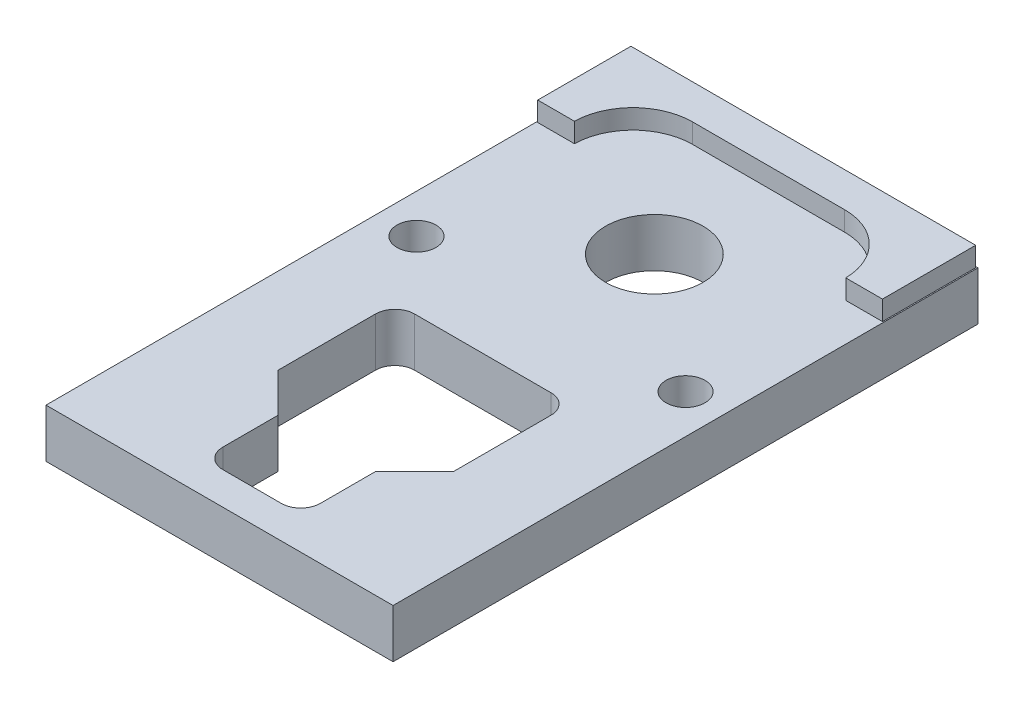
SolidWorks part; units mm, degrees
ref_plane "Płaszczyzna przednia" through (0, 0, 0) normal (0, 0, 1) x (1, 0, 0)
ref_plane "Płaszczyzna górna" through (0, 0, 0) normal (0, 1, 0) x (1, 0, 0)
ref_plane "Płaszczyzna prawa" through (0, 0, 0) normal (1, 0, 0) x (0, 0, -1)
sketch "Sketch1" plane through (0, 0, 0) normal (0, 1, 0) x (1, 0, 0)
  line L0 (-6.9, 0) -> (6.9, 0) construction
  line L2 (-8.9, 13) -> (8.9, 13)
  line L3 (-8.9, 13) -> (-8.9, -17)
  line L4 (-8.9, -17) -> (8.9, -17)
  line L5 (8.9, 13) -> (8.9, -17)
  circle A0 centre (-6.9, 0) radius 1
  circle A1 centre (6.9, 0) radius 1
  circle A2 centre (6.9, 0) radius 2 construction
  circle A3 centre (-6.9, 0) radius 2 construction
  circle A4 centre (0, 5.3) radius 2.5
  point P4 (0, 0)
  dimension "D2" = 2
  dimension "D4" = 5
  dimension "D5" = 5.3
  dimension "D1" = 13.8
  dimension "D6" = 13
  dimension "D7" = 17
  dimension "D3" = 1
extrude "Boss-Extrude1" add sketch "Sketch1" along normal blind 2.5
sketch "Sketch2" plane through (0, 2.5, 0) normal (0, 1, 0) x (1, 0, 0)
  line L0 (0, -3.5) -> (0, 0) construction
  line L1 (-4.5, -3.5) -> (4.5, -3.5)
  line L2 (-4.5, -3.5) -> (-4.5, -9.5)
  line L3 (-4.5, -9.5) -> (4.5, -9.5)
  line L4 (4.5, -3.5) -> (4.5, -9.5)
  line L5 (0, -15.3309) -> (0, 0) construction
  line L6 (-2.5, -9.5) -> (2.5, -9.5)
  line L7 (-2.5, -9.5) -> (-2.5, -15.3309)
  line L8 (-2.5, -15.3309) -> (2.5, -15.3309)
  line L9 (2.5, -9.5) -> (2.5, -15.3309)
  dimension "D1" = 9
  dimension "D2" = 6
  dimension "D3" = 3.5
  dimension "D4" = 5
extrude "Cut-Extrude1" cut sketch "Sketch2" against normal through all contours L4 L1 L2 L3 | L9 L3 L7 L8 region at (0, 2.5, 6.5) region at (0, 2.5, 12.4155)
chamfer "Chamfer1" distance 2 angle 45 2 edges at (2.5, 1.25, 9.5) (-2.5, 1.25, 9.5)
fillet "Fillet1" radius 1 4 edges at (2.5, 1.25, 15.3309) (-2.5, 1.25, 15.3309) (4.5, 1.25, 3.5) (-4.5, 1.25, 3.5)
sketch "Sketch3" plane through (0, 2.5, 0) normal (0, 1, 0) x (1, 0, 0)
  line L0 (-3.9, 11.1) -> (3.9, 11.1) construction
  line L1 (-3.9, 11.1) -> (3.9, 11.1) construction
  line L2 (-6.9, 8.1) -> (-8.9, 8.1) construction
  line L3 (-8.9, 13) -> (-8.9, -17) construction
  line L4 (-8.9, 8.1) -> (-8.9, 13) construction
  line L5 (-8.9, 13) -> (8.9, 13) construction
  line L6 (8.9, 13) -> (8.9, 8.1) construction
  line L7 (8.9, -17) -> (8.9, 13) construction
  line L8 (8.9, 8.1) -> (6.9, 8.1) construction
  line L9 (8.84, 8.16) -> (6.9594, 8.16)
  line L10 (-3.9, 11.16) -> (3.9, 11.16)
  line L11 (-6.9594, 8.16) -> (-8.84, 8.16)
  line L12 (-8.84, 8.16) -> (-8.84, 12.94)
  line L13 (-8.84, 12.94) -> (8.84, 12.94)
  line L14 (8.84, 12.94) -> (8.84, 8.16)
  arc A0 (6.9, 8.1) -> (3.9, 11.1) centre (3.8989, 8.0989) ccw construction
  arc A1 (-3.9, 11.1) -> (-6.9, 8.1) centre (-3.8989, 8.0989) ccw construction
  arc A2 (6.9, 8.1) -> (3.9, 11.1) centre (3.8989, 8.0989) ccw construction
  arc A3 (-3.9, 11.1) -> (-6.9, 8.1) centre (-3.8989, 8.0989) ccw construction
  arc A4 (6.9594, 8.16) -> (3.9, 11.16) centre (3.8989, 8.0989) ccw
  arc A5 (-3.9, 11.16) -> (-6.9594, 8.16) centre (-3.8989, 8.0989) ccw
  dimension "D1" = 0.06
extrude "Boss-Extrude2" add sketch "Sketch3" along normal blind 1
